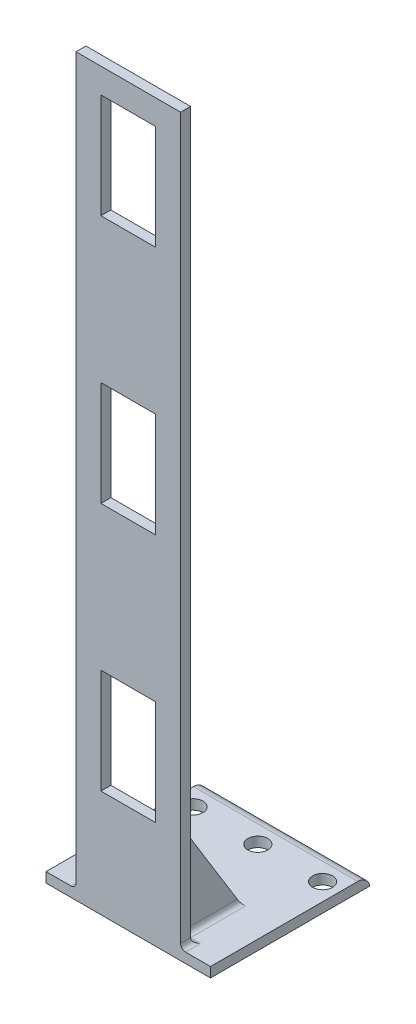
SolidWorks part; units mm, degrees
ref_plane "Front Plane" through (0, 0, 0) normal (0, 0, 1) x (1, 0, 0)
ref_plane "Top Plane" through (0, 0, 0) normal (0, 1, 0) x (1, 0, 0)
ref_plane "Right Plane" through (0, 0, 0) normal (1, 0, 0) x (0, 0, -1)
sketch "Sketch1" plane through (0, 0, 0) normal (0, 0, 1) x (1, 0, 0)
  line L0 (0, -1000) -> (0, 49000) construction
  line L1 (-10.5, -72.75) -> (10.5, -72.75)
  line L2 (-10.5, -72.75) -> (-10.5, 72.75)
  line L3 (-10.5, 72.75) -> (10.5, 72.75)
  line L4 (10.5, -72.75) -> (10.5, 72.75)
  line L5 (-10.5, -72.75) -> (10.5, 72.75) construction
  line L6 (-10.5, 72.75) -> (10.5, -72.75) construction
  line L8 (-5.5, -53.25) -> (5.5, -53.25)
  line L9 (-5.5, -53.25) -> (-5.5, -32.25)
  line L10 (-5.5, -32.25) -> (5.5, -32.25)
  line L11 (5.5, -53.25) -> (5.5, -32.25)
  line L12 (-5.5, -53.25) -> (5.5, -32.25) construction
  line L13 (-5.5, -32.25) -> (5.5, -53.25) construction
  line L14 (-5.5, 17.75) -> (5.5, 17.75)
  line L15 (-5.5, 17.75) -> (-5.5, -3.25)
  line L16 (-5.5, -3.25) -> (5.5, -3.25)
  line L17 (5.5, 17.75) -> (5.5, -3.25)
  line L18 (-5.5, 17.75) -> (5.5, -3.25) construction
  line L19 (-5.5, -3.25) -> (5.5, 17.75) construction
  line L20 (-5.5, 67.75) -> (5.5, 67.75)
  line L21 (-5.5, 67.75) -> (-5.5, 46.75)
  line L22 (-5.5, 46.75) -> (5.5, 46.75)
  line L23 (5.5, 67.75) -> (5.5, 46.75)
  line L24 (-5.5, 67.75) -> (5.5, 46.75) construction
  line L25 (-5.5, 46.75) -> (5.5, 67.75) construction
  point P0 (0, 0)
  point P6 (0, -42.75)
  point P13 (0, 7.25)
  point P18 (0, 57.25)
  dimension "D1" = 21
  dimension "D2" = 145.5
  dimension "D3" = 11
  dimension "D4" = 21
  dimension "D5" = 11
  dimension "D6" = 21
  dimension "D7" = 29
  dimension "D8" = 19.5
  dimension "D9" = 11
  dimension "D10" = 21
  dimension "D11" = 29
  dimension "D12" = 5
extrude "Boss-Extrude1" add sketch "Sketch1" along normal blind 2
sketch "Sketch2" plane through (0, 0, 0) normal (0, 0, -1) x (-1, 0, 0)
  line L4 (10.5, -72.75) -> (16.5, -72.75)
  line L9 (16.5, -72.75) -> (16.5, -74.75)
  line L10 (16.5, -74.75) -> (-16.5, -74.75)
  line L11 (-16.5, -74.75) -> (-16.5, -72.75)
  line L12 (-16.5, -72.75) -> (10.5, -72.75)
  dimension "D1" = 2
  dimension "D2" = 33
  dimension "D3" = 6
extrude "Boss-Extrude2" add sketch "Sketch2" along normal blind 30 and the other way blind 2
ref_plane "Plane1" through (7.5, 0, 0) normal (1, 0, 0) x (0, 0, -1)
ref_plane "Plane2" through (-7.5, 0, 0) normal (1, 0, 0) x (0, 0, -1)
fillet "Fillet2" radius 2.5 1 edges at (0, -72.75, -30)
sketch "Sketch6" plane through (0, -72.75, 0) normal (0, 1, 0) x (1, 0, 0)
  line L0 (16.5, 30) -> (-16.5, 30) construction
  circle A0 centre (0, 24) radius 2
  dimension "D1" = 4
  dimension "D2" = 6
extrude "Cut-Extrude1" cut sketch "Sketch6" against normal blind 2
sketch "Sketch7" plane through (7.5, 0, 0) normal (1, 0, 0) x (0, 0, -1)
  line L0 (0, -53.25) -> (12, -72.75)
  line L1 (-2, -72.75) -> (27.5505, -72.75) construction
  line L2 (12, -72.75) -> (0, -72.75)
  line L3 (0, -72.75) -> (0, -53.25)
  dimension "D1" = 19.5
  dimension "D2" = 12
extrude "Boss-Extrude5" add sketch "Sketch7" along normal mid plane 2
sketch "Sketch8" plane through (-7.5, 0, 0) normal (1, 0, 0) x (0, 0, -1)
  line L0 (12, -72.75) -> (0, -53.25)
  line L1 (0, -53.25) -> (0, -72.75)
  line L2 (0, -72.75) -> (12, -72.75)
extrude "Boss-Extrude6" add sketch "Sketch8" along normal mid plane 2
sketch "Sketch9" plane through (0, -74.75, 0) normal (0, -1, 0) x (1, 0, 0)
  line L0 (0, -24) -> (13, -24) construction
  line L1 (0, -1008.7827) -> (0, 48991.2173) construction
  circle A0 centre (13, -24) radius 2
  circle A1 centre (-13, -24) radius 2
  dimension "D1" = 4
  dimension "D2" = 13
extrude "Cut-Extrude2" cut sketch "Sketch9" against normal blind 2
fillet "Fillet3" radius 1 9 edges at (-6.5, -72.75, -6) (-10.5, -72.75, 1) (-9.5, -72.75, 0) (-8.5, -72.75, -6) (6.5, -72.75, -6) (10.5, -72.75, 1) (8.5, -72.75, -6) (9.5, -72.75, 0) (0, -72.75, 0)
